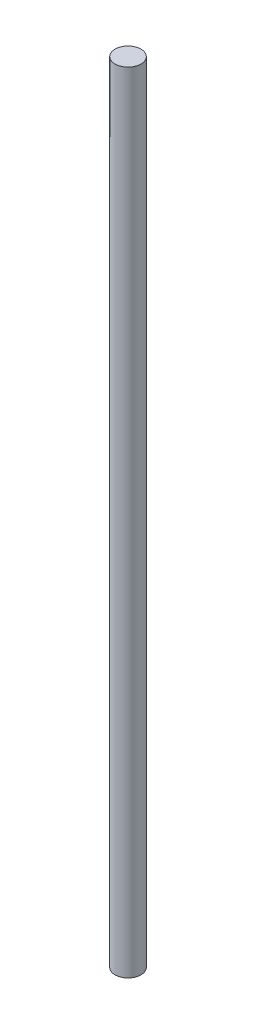
SolidWorks part; units mm, degrees
material "1060 Alloy"
ref_plane "Front Plane" through (0, 0, 0) normal (0, 0, 1) x (1, 0, 0)
ref_plane "Top Plane" through (0, 0, 0) normal (0, 1, 0) x (1, 0, 0)
ref_plane "Right Plane" through (0, 0, 0) normal (1, 0, 0) x (0, 0, -1)
sketch "Sketch1" plane through (0, 0, 0) normal (0, 1, 0) x (1, 0, 0)
  circle A0 centre (0, 0) radius 5
  dimension "D1" = 10
extrude "Boss-Extrude1" add sketch "Sketch1" along normal blind 304.8
